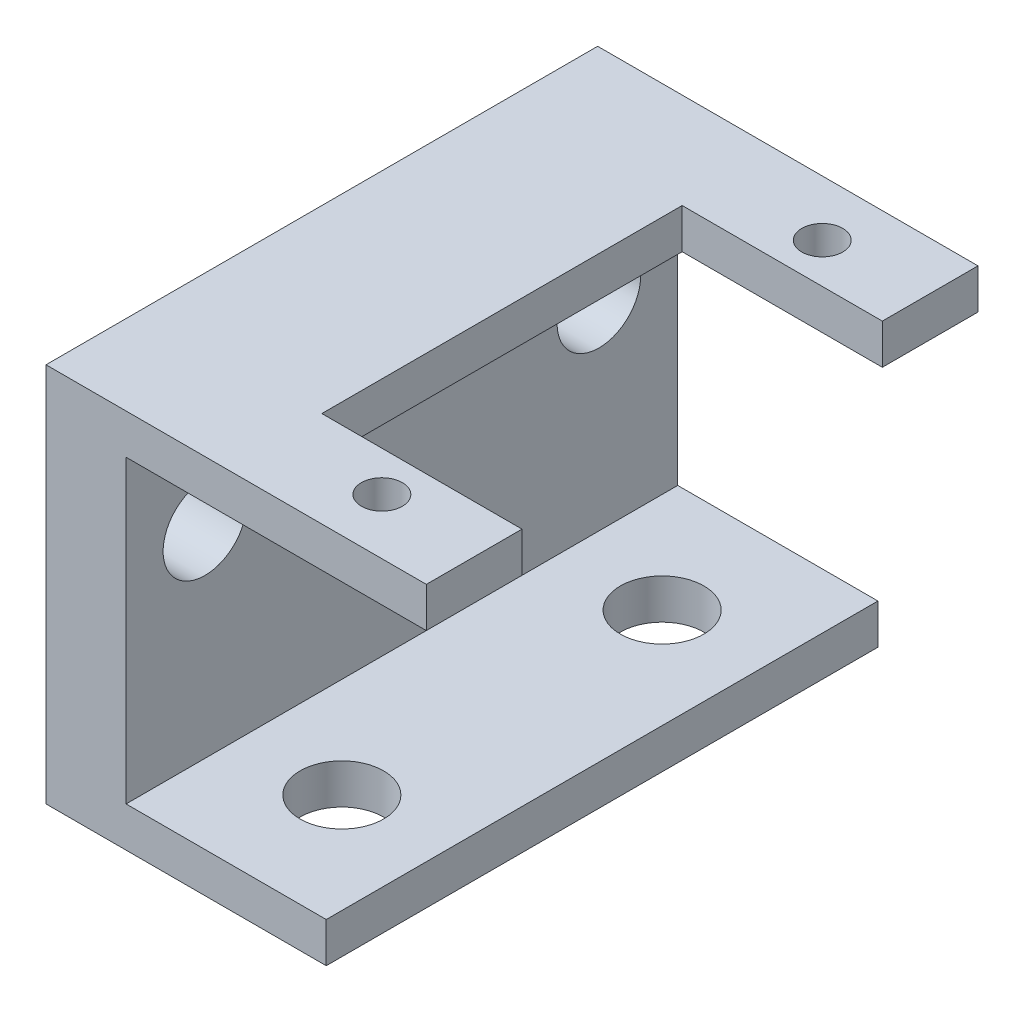
SolidWorks part; units mm, degrees
ref_plane "Front Plane" through (0, 0, 0) normal (0, 0, 1) x (1, 0, 0)
ref_plane "Top Plane" through (0, 0, 0) normal (0, 1, 0) x (1, 0, 0)
ref_plane "Right Plane" through (0, 0, 0) normal (1, 0, 0) x (0, 0, -1)
sketch "Sketch1" plane through (0, 0, 0) normal (0, 0, 1) x (1, 0, 0)
  line L1 (0, 0) -> (17.78, 0)
  line L2 (0, 0) -> (0, 2.54)
  line L3 (0, 2.54) -> (17.78, 2.54)
  line L4 (17.78, 0) -> (17.78, 2.54)
  line L5 (0, 2.54) -> (5.08, 2.54)
  line L6 (0, 2.54) -> (0, 21.59)
  line L7 (0, 21.59) -> (5.08, 21.59)
  line L8 (5.08, 2.54) -> (5.08, 21.59)
  line L9 (0, 21.59) -> (24.13, 21.59)
  line L10 (0, 21.59) -> (0, 24.13)
  line L11 (0, 24.13) -> (24.13, 24.13)
  line L12 (24.13, 21.59) -> (24.13, 24.13)
  dimension "D1" = 5.08
  dimension "D2" = 12.7
  dimension "D3" = 19.05
  dimension "D4" = 2.54
  dimension "D5" = 2.54
  dimension "D6" = 19.05
extrude "Boss-Extrude1" add sketch "Sketch1" along normal blind 35 contours L9 L12 L11 L10 L7 | L6 L5 L8 L7 | L2 L1 L4 L3 region at (12.065, 22.86, 0)
hole_wizard "Ø5.0mm Dowel Hole1" positions "Sketch2" profile "Sketch3" hole size "Ø5.0" standard "ANSI Metric" end condition through all
sketch "Sketch2" plane through (5.08, 0, 0) normal (1, 0, 0) x (0, 0, -1)
  line L3 (-35, 2.54) -> (0, 2.54) construction
  line L6 (-30, 15.24) -> (-5, 15.24) construction
  line L8 (-35, 0) -> (0, 0) construction
  point P0 (-30, 15.24)
  point P2 (-5, 15.24)
  point P30 (-17.5, 0)
  point P31 (-17.5, 15.24)
  dimension "D1" = 25
  dimension "D3" = 12.7
sketch "Sketch3" plane through (5.08, 15.24, 30) normal (0, 1, 0) x (0, 0, -1)
  line L0 (0, 0) -> (0, 5.08)
  line L1 (0, 5.08) -> (2.65, 5.08)
  line L2 (2.65, 5.08) -> (2.65, 0)
  line L5 (2.65, 0) -> (0, 0)
  line L11 (0, -6.35) -> (0, 107.95) construction
  dimension "Thru Hole Dia." = 5.3
  dimension "Thru Hole Depth" = 5.08
hole_wizard "Ø5.0mm Dowel Hole2" positions "Sketch4" profile "Sketch5" hole size "Ø5.0" standard "ANSI Metric" end condition through all
sketch "Sketch4" plane through (0, 2.54, 0) normal (0, 1, 0) x (1, 0, 0)
  line L2 (11.43, -7.34) -> (11.43, -27.66) construction
  line L5 (5.08, -35) -> (5.08, 0) construction
  line L6 (17.78, -35) -> (17.78, 0) construction
  point P0 (11.43, -27.66)
  point P2 (11.43, -7.34)
  point P25 (17.78, -17.5)
  point P26 (11.43, -17.5)
  dimension "D1" = 20.32
  dimension "D2" = 6.35
sketch "Sketch5" plane through (11.43, 2.54, 27.66) normal (1, 0, 0) x (0, 0, 1)
  line L0 (0, 0) -> (0, 2.54)
  line L1 (0, 2.54) -> (2.65, 2.54)
  line L2 (2.65, 2.54) -> (2.65, 0)
  line L5 (2.65, 0) -> (0, 0)
  line L11 (0, -6.35) -> (0, 107.95) construction
  dimension "Thru Hole Dia." = 5.3
  dimension "Thru Hole Depth" = 2.54
sketch "Sketch6" plane through (0, 24.13, 0) normal (0, 1, 0) x (1, 0, 0)
  line L0 (24.13, -35) -> (24.13, 0) construction
  line L1 (24.13, -6.07) -> (11.43, -6.07)
  line L2 (24.13, -6.07) -> (24.13, -28.93)
  line L3 (24.13, -28.93) -> (11.43, -28.93)
  line L4 (11.43, -6.07) -> (11.43, -28.93)
  line L5 (0, 0) -> (24.13, 0) construction
  line L6 (0, -35) -> (24.13, -35) construction
  line L9 (17.78, -6.07) -> (17.78, 0) construction
  line L10 (17.78, -28.93) -> (17.78, -35) construction
  dimension "D2" = 12.7
  dimension "D1" = 22.86
extrude "Cut-Extrude1" cut sketch "Sketch6" against normal up to next contours L2 L1 L4 L3
hole_wizard "M2 Clearance Hole1" positions "Sketch7" profile "Sketch8" hole size "M2" standard "ANSI Metric" end condition up to next
sketch "Sketch7" plane through (0, 24.13, 0) normal (0, 1, 0) x (1, 0, 0)
  line L0 (17.78, -28.93) -> (17.78, -35) construction
  line L1 (17.78, -6.07) -> (17.78, 0) construction
  line L2 (11.43, -6.07) -> (11.43, -28.93) construction
  point P0 (17.78, -31.47)
  point P4 (17.78, -3.53)
  point P13 (11.43, -17.5)
  dimension "D1" = 13.97
  dimension "D2" = 13.97
sketch "Sketch8" plane through (17.78, 24.13, 31.47) normal (1, 0, 0) x (0, 0, 1)
  line L0 (0, 0) -> (0, 2.54)
  line L1 (0, 2.54) -> (1.3, 2.54)
  line L2 (1.3, 2.54) -> (1.3, 0)
  line L5 (1.3, 0) -> (0, 0)
  line L11 (0, -6.35) -> (0, 107.95) construction
  dimension "Thru Hole Dia." = 2.6
  dimension "Thru Hole Depth" = 2.54
equation "\"wall thicc\"= 2.5mm"
equation "\"press fit\"= 0.3mm"
equation "\"shaft thick\"= 5mm + \"press fit\""
equation "\"D1@Sketch1\"=\"wall thicc\"*2"
equation "\"D4@Sketch1\"=\"wall thicc\""
equation "\"D5@Sketch1\"=\"wall thicc\""
equation "\"servo width\"= 22.5mm"
equation "\"D1@Sketch6\"=\"servo width\"+\"press fit\""
equation "\"servo length\"= 12.5mm"
equation "\"D2@Sketch6\"=\"servo length\"+\"press fit\""
equation "\"servo hole spacing\"= 13.9mm"
equation "\"D1@Sketch7\"=\"servo hole spacing\""
equation "\"D2@Sketch7\"=\"servo hole spacing\""
